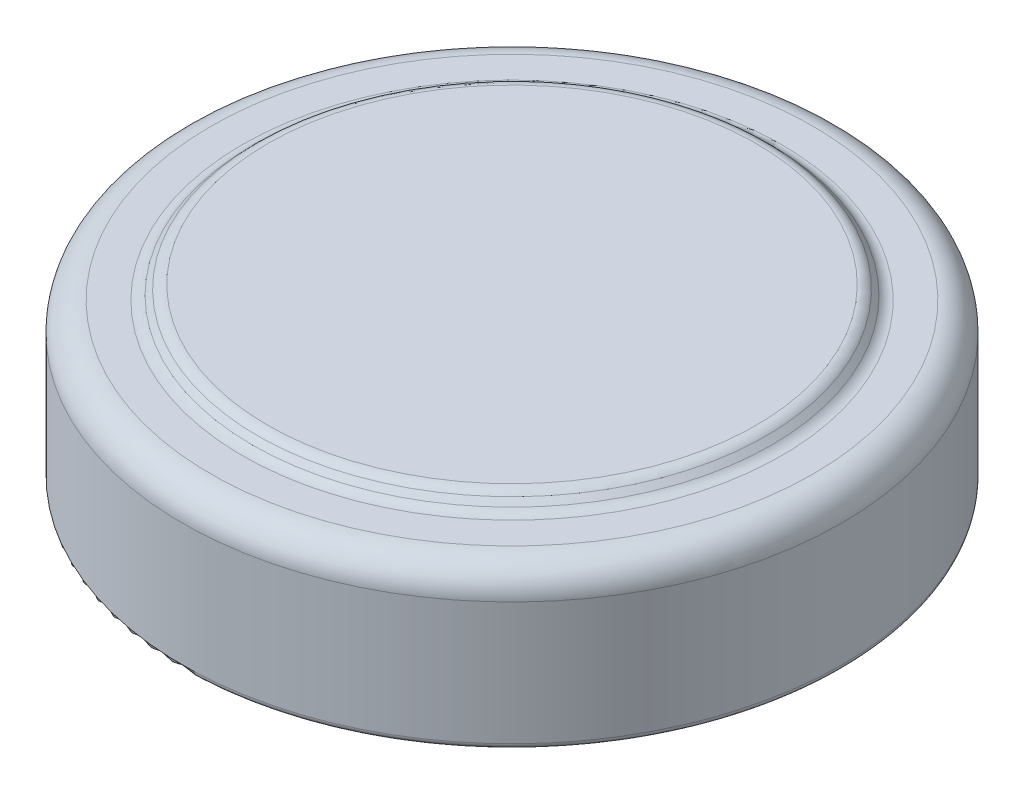
SolidWorks part; units mm, degrees
ref_plane "Front Plane" through (0, 0, 0) normal (0, 0, 1) x (1, 0, 0)
ref_plane "Top Plane" through (0, 0, 0) normal (0, 1, 0) x (1, 0, 0)
ref_plane "Right Plane" through (0, 0, 0) normal (1, 0, 0) x (0, 0, -1)
sketch "Sketch1" plane through (0, 0, 0) normal (0, 0, 1) x (1, 0, 0)
  line L0 (0, 0) -> (-5.7, 0)
  line L1 (-5.8, 0.1) -> (-5.8, 2.26)
  line L2 (-4.2964, 3) -> (0, 3)
  line L3 (0, 3) -> (0, 0)
  line L4 (-4.4732, 2.9268) -> (-4.5668, 2.8332)
  line L7 (-5.3, 2.76) -> (-4.7436, 2.76)
  arc A0 (-5.8, 2.26) -> (-5.3, 2.76) centre (-5.3, 2.26) cw
  arc A1 (-4.4732, 2.9268) -> (-4.2964, 3) centre (-4.2964, 2.75) cw
  arc A2 (-4.7436, 2.76) -> (-4.5668, 2.8332) centre (-4.7436, 3.01) ccw
  arc A3 (-5.7, 0) -> (-5.8, 0.1) centre (-5.7, 0.1) cw
  point P9 (-5.8, 2.76)
  point P14 (-4.4, 3)
  point P17 (-5.8, 0)
  point P18 (-4.64, 2.76)
  dimension "D6" = 0.5
  dimension "D7" = 0.25
  dimension "D8" = 0.1
  dimension "D1" = 5.8
  dimension "D2" = 3
  dimension "D3" = 4.64
  dimension "D4" = 2.76
  dimension "D5" = 45
revolve "Revolve1" add sketch "Sketch1" angle 360 about L3
sketch "Sketch2" plane through (0, 0, 0) normal (0, -1, 0) x (1, 0, 0)
  line L0 (0.25, -0.25) -> (0.25, -2)
  line L1 (-0.25, 2) -> (0.25, 2)
  line L2 (-0.25, 2) -> (-0.25, 0.25)
  line L3 (-0.25, -2) -> (0.25, -2)
  line L4 (0.25, 2) -> (0.25, 0.25)
  line L5 (-2, 0.25) -> (-0.25, 0.25)
  line L6 (-2, 0.25) -> (-2, -0.25)
  line L7 (-2, -0.25) -> (-0.25, -0.25)
  line L8 (2, 0.25) -> (2, -0.25)
  line L9 (-0.25, -0.25) -> (-0.25, -2)
  line L10 (0.25, 0.25) -> (2, 0.25)
  line L11 (0.25, -0.25) -> (2, -0.25)
  circle A0 centre (0, 0) radius 4 construction
  text T0 "                                 LR54" font "Century Gothic" height 1
  dimension "D1" = 8
  dimension "D2" = 0.25
  dimension "D3" = 0.5
  dimension "D4" = 0.25
  dimension "D5" = 0.5
  dimension "D6" = 4
  dimension "D7" = 4
  dimension "D8" = 2
  dimension "D9" = 2
wrap "Wrap1" sketch "Sketch2" wrap type scribe source sketch "Sketch2" face at (-5.7, 0, 0)
